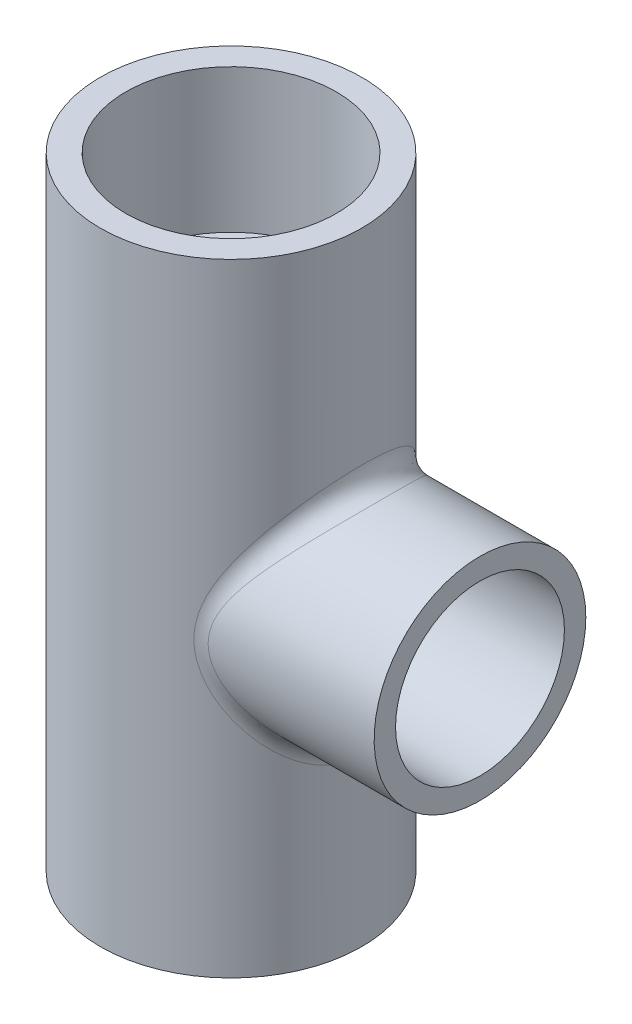
SolidWorks part; units mm, degrees
ref_plane "Front Plane" through (0, 0, 0) normal (0, 0, 1) x (1, 0, 0)
ref_plane "Top Plane" through (0, 0, 0) normal (0, 1, 0) x (1, 0, 0)
ref_plane "Right Plane" through (0, 0, 0) normal (1, 0, 0) x (0, 0, -1)
sketch "Sketch1" plane through (0, 0, 0) normal (0, 1, 0) x (1, 0, 0)
  circle A0 centre (0, 0) radius 13.4366
  circle A1 centre (0, 0) radius 10.4648
  circle A2 centre (0, 0) radius 16.6751
  dimension "D1" = 26.8732
  dimension "D2" = 33.3502
  dimension "t" = 20.9296
extrude "Boss-Extrude1" add sketch "Sketch1" along normal blind 79.375 contours A2
extrude "Cut-Extrude1" cut sketch "Sketch1<4>" along normal through all and the other way through all contours A1 region at (0, 0, 0)
sketch "Sketch1<4>" plane through (0, 0, 0) normal (0, 1, 0) x (1, 0, 0) same geometry as "Sketch1"
extrude "Cut-Extrude2" cut sketch "Sketch1<5>" along normal blind 18.288 contours A0 A1 region at (-13.0566, 0, 0)
sketch "Sketch1<5>" plane through (0, 0, 0) normal (0, 1, 0) x (1, 0, 0) same geometry as "Sketch1"
sketch "Sketch2" plane through (0, 79.375, 0) normal (0, 1, 0) x (1, 0, 0)
  circle A0 centre (0, 0) radius 13.4366
  circle A1 centre (0, 0) radius 10.4648
  dimension "D1" = 20.9296
  dimension "D2" = 26.8732
extrude "Cut-Extrude3" cut sketch "Sketch2" against normal blind 18.288
sketch "Sketch3" plane through (0, 0, 0) normal (1, 0, 0) x (0, 0, -1)
  line L0 (0, -2.939) -> (0, 77.2759) construction
  circle A0 centre (0, 37.1684) radius 7.8994
  circle A1 centre (0, 37.1684) radius 10.7696
  circle A2 centre (0, 37.1684) radius 13.5001
  dimension "D1" = 15.7988
  dimension "D2" = 21.5392
  dimension "D3" = 27.0002
extrude "Boss-Extrude2" add sketch "Sketch3" along normal blind 31.75 contours A2
sketch "Sketch4" plane through (31.75, 0, 0) normal (1, 0, 0) x (0, 0, -1)
  line L0 (0, -2.939) -> (0, 77.2759) construction
  circle A0 centre (0, 37.1684) radius 7.8994
  circle A1 centre (0, 37.1684) radius 10.7696
  dimension "D1" = 15.7988
  dimension "D2" = 21.5392
extrude "Cut-Extrude5" cut sketch "Sketch3<7>" along normal blind 33.3502 contours A0
sketch "Sketch3<7>" plane through (0, 0, 0) normal (1, 0, 0) x (0, 0, -1) same geometry as "Sketch3"
extrude "Cut-Extrude6" cut sketch "Sketch4" against normal blind 17.526
fillet "Fillet1" radius 2.54 1 edges at (10.0299, 39.3577, -13.3214)
